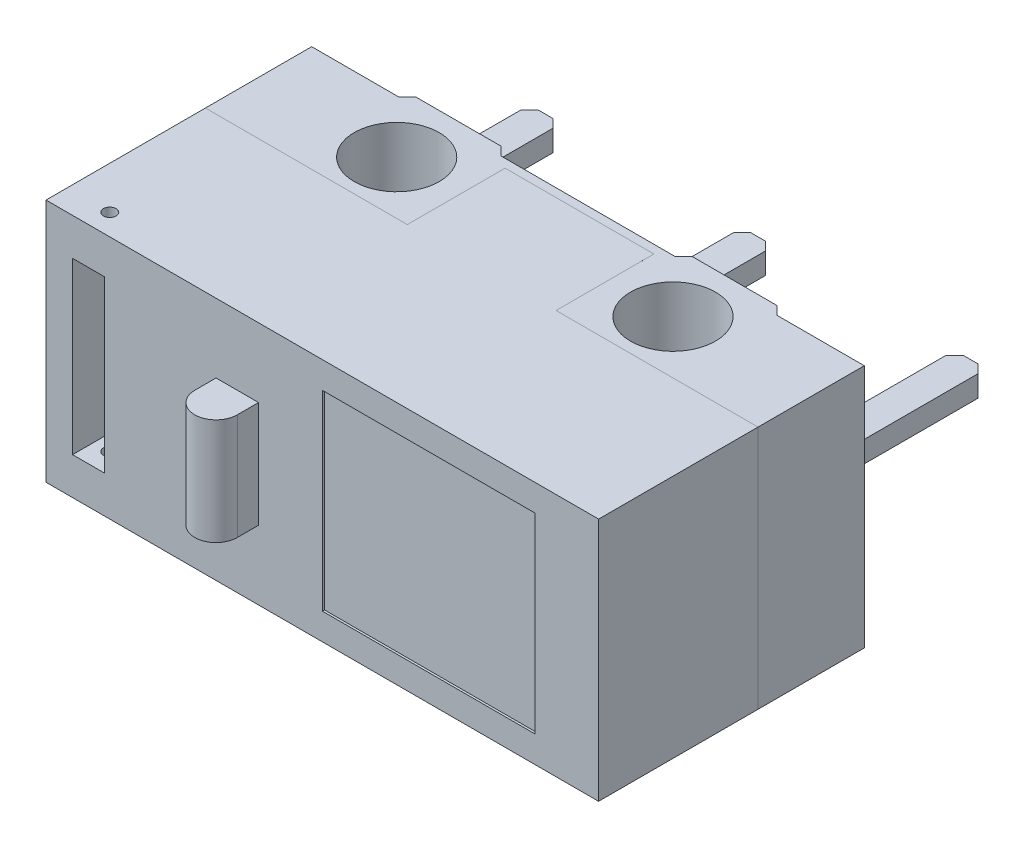
SolidWorks part; units mm, degrees
ref_plane "Front Plane" through (0, 0, 0) normal (0, 0, 1) x (1, 0, 0)
ref_plane "Top Plane" through (0, 0, 0) normal (0, 1, 0) x (1, 0, 0)
ref_plane "Right Plane" through (0, 0, 0) normal (1, 0, 0) x (0, 0, -1)
sketch "Sketch1" plane through (0, 0, 0) normal (0, 0, 1) x (1, 0, 0)
  line L1 (-6.5, 2.875) -> (6.5, 2.875)
  line L2 (-6.5, 2.875) -> (-6.5, -2.875)
  line L3 (-6.5, -2.875) -> (6.5, -2.875)
  line L4 (6.5, 2.875) -> (6.5, -2.875)
  line L5 (-6.5, 2.875) -> (6.5, -2.875) construction
  line L6 (-6.5, -2.875) -> (6.5, 2.875) construction
  point P0 (0, 0)
  dimension "D1" = 13
  dimension "D2" = 5.75
extrude "Boss-Extrude1" add sketch "Sketch1" along normal blind 2.5
sketch "Sketch2" plane through (0, 0, 0) normal (0, 0, -1) x (-1, 0, 0)
  line L1 (-0.375, 0.25) -> (0.375, 0.25)
  line L2 (-0.375, 0.25) -> (-0.375, -0.25)
  line L3 (-0.375, -0.25) -> (0.375, -0.25)
  line L4 (0.375, 0.25) -> (0.375, -0.25)
  line L5 (-0.375, 0.25) -> (0.375, -0.25) construction
  line L6 (-0.375, -0.25) -> (0.375, 0.25) construction
  line L7 (-5.375, 0.25) -> (-4.625, 0.25)
  line L8 (-5.375, 0.25) -> (-5.375, -0.25)
  line L9 (-5.375, -0.25) -> (-4.625, -0.25)
  line L10 (-4.625, 0.25) -> (-4.625, -0.25)
  line L11 (-5.375, 0.25) -> (-4.625, -0.25) construction
  line L12 (-5.375, -0.25) -> (-4.625, 0.25) construction
  line L13 (4.625, 0.25) -> (5.375, 0.25)
  line L14 (4.625, 0.25) -> (4.625, -0.25)
  line L15 (4.625, -0.25) -> (5.375, -0.25)
  line L16 (5.375, 0.25) -> (5.375, -0.25)
  line L17 (4.625, 0.25) -> (5.375, -0.25) construction
  line L18 (4.625, -0.25) -> (5.375, 0.25) construction
  point P0 (0, 0)
  point P6 (-5, 0)
  point P11 (5, 0)
  dimension "D1" = 0.5
  dimension "D2" = 0.5
  dimension "D3" = 0.5
  dimension "D4" = 0.75
  dimension "D5" = 0.75
  dimension "D6" = 0.75
  dimension "D7" = 5
  dimension "D8" = 5
  dimension "D9" = 0
  dimension "D10" = 0
extrude "Boss-Extrude2" add sketch "Sketch2" along normal blind 4
chamfer "Chamfer1" distance 0.2 angle 45 6 edges at (-5.375, 0, -4) (-4.625, 0, -4) (-0.375, 0, -4) (0.375, 0, -4) (4.625, 0, -4) (5.375, 0, -4)
sketch "Sketch4" plane through (0, 2.875, 0) normal (0, 1, 0) x (1, 0, 0)
  line L0 (6.5, 0) -> (-6.5, 0) construction
  circle A0 centre (-3.25, -1.25) radius 1
  circle A1 centre (3.25, -1.25) radius 1
  dimension "D5" = 2
  dimension "D6" = 2
  dimension "D1" = 6.5
  dimension "D2" = 3.25
  dimension "D3" = 1.25
  dimension "D4" = 1.25
extrude "Cut-Extrude1" cut sketch "Sketch4" against normal blind 6
sketch "Sketch5" plane through (0, 2.875, 0) normal (0, 1, 0) x (1, 0, 0)
  line L0 (6.5, 0) -> (-6.5, 0) construction
  line L1 (-4.25, 0) -> (-2.25, 0)
  line L2 (-4.25, 0) -> (-4.25, 0.2)
  line L3 (-4.25, 0.2) -> (-2.25, 0.2)
  line L4 (-2.25, 0) -> (-2.25, 0.2)
  line L5 (4.25, 0) -> (2.25, 0)
  line L6 (4.25, 0) -> (4.25, 0.2)
  line L7 (4.25, 0.2) -> (2.25, 0.2)
  line L8 (2.25, 0) -> (2.25, 0.2)
  circle A0 centre (-3.25, -1.25) radius 1 construction
  circle A1 centre (3.25, -1.25) radius 1 construction
  dimension "D1" = 2
  dimension "D2" = 2
  dimension "D3" = 0
  dimension "D4" = 0
  dimension "D5" = 1
  dimension "D6" = 1
  dimension "D7" = 0.2
  dimension "D8" = 0.2
extrude "Boss-Extrude3" add sketch "Sketch5" against normal blind 5.75
chamfer "Chamfer2" distance 0.2 angle 45 4 edges at (4.25, 0, 0) (2.25, 0, 0) (-2.25, 0, 0) (-4.25, 0, 0)
sketch "Sketch10" plane through (0, 0, 2.5) normal (0, 0, 1) x (1, 0, 0)
  line L0 (-6.5, 2.875) -> (-6.5, -2.875) construction
  line L1 (-6.5001, 2.8751) -> (6.5001, 2.8751)
  line L2 (-6.5001, 2.8751) -> (-6.5001, -2.8751)
  line L3 (-6.5001, -2.8751) -> (6.5001, -2.8751)
  line L4 (6.5001, 2.8751) -> (6.5001, -2.8751)
  line L5 (6.5, 2.875) -> (-6.5, 2.875) construction
  line L6 (6.5, -2.875) -> (6.5, 2.875) construction
  line L7 (-6.5, -2.875) -> (6.5, -2.875) construction
  dimension "D1" = 0.0001
  dimension "D2" = 0.0001
  dimension "D3" = 0.0001
  dimension "D4" = 0.0001
extrude "Boss-Extrude8" add sketch "Sketch10" along normal blind 3.75
sketch "Sketch11" plane through (0, -2.8751, 0) normal (0, -1, 0) x (1, 0, 0)
  line L0 (-6.5, 2.5) -> (6.5, 2.5) construction
  line L1 (-1.75, 2.5) -> (1.75, 2.5)
  line L2 (-1.75, 2.5) -> (-1.75, 0.2)
  line L3 (-1.75, 0.2) -> (1.75, 0.2)
  line L4 (1.75, 2.5) -> (1.75, 0.2)
  line L5 (-2.05, 0) -> (2.05, 0) construction
  point P8 (0, 0)
  dimension "D1" = 3.5
  dimension "D2" = 0
  dimension "D3" = 0.2
  dimension "D4" = 1.75
extrude "Boss-Extrude9" add sketch "Sketch11" against normal blind 0.5
sketch "Sketch12" plane through (0, 2.8751, 0) normal (0, 1, 0) x (1, 0, 0)
  line L0 (6.5, -2.5) -> (-6.5, -2.5) construction
  line L1 (1.75, -2.5) -> (-1.75, -2.5)
  line L2 (1.75, -2.5) -> (1.75, -0.2)
  line L3 (1.75, -0.2) -> (-1.75, -0.2)
  line L4 (-1.75, -2.5) -> (-1.75, -0.2)
  line L5 (2.05, 0) -> (-2.05, 0) construction
  point P8 (0, 0)
  dimension "D1" = 0
  dimension "D2" = 0.2
  dimension "D3" = 1.75
  dimension "D4" = 3.5
extrude "Boss-Extrude10" add sketch "Sketch12" against normal blind 0.5
sketch "Sketch13" plane through (0, 0, 6.25) normal (0, 0, 1) x (1, 0, 0)
  line L0 (6.5001, -2.8751) -> (6.5001, 2.8751) construction
  line L1 (-2.4999, 1.25) -> (-1.4999, 1.25)
  line L2 (-2.4999, 1.25) -> (-2.4999, -1.25)
  line L3 (-2.4999, -1.25) -> (-1.4999, -1.25)
  line L4 (-1.4999, 1.25) -> (-1.4999, -1.25)
  dimension "D1" = 2.5
  dimension "D2" = 1.25
  dimension "D3" = 1
  dimension "D4" = 9
extrude "Boss-Extrude11" add sketch "Sketch13" along normal blind 1
fillet "Fillet2" 2 edges at (-2.4999, 0, 7.25) (-1.4999, 0, 7.25) type full round first side face at (-2.4999, 0, 6.75) second side face at (-1.4999, 0, 6.75) middle face at (-1.9999, 0, 7.25)
sketch "Sketch14" plane through (0, 0, 6.25) normal (0, 0, 1) x (1, 0, 0)
  line L0 (6.5001, -2.8751) -> (6.5001, 2.8751) construction
  line L1 (0.0001, 2.25) -> (5.0001, 2.25)
  line L2 (0.0001, 2.25) -> (0.0001, -2.25)
  line L3 (0.0001, -2.25) -> (5.0001, -2.25)
  line L4 (5.0001, 2.25) -> (5.0001, -2.25)
  dimension "D1" = 5
  dimension "D2" = 4.5
  dimension "D3" = 2.25
  dimension "D4" = 1.5
extrude "Cut-Extrude2" cut sketch "Sketch14" against normal blind 0.05
sketch "Sketch15" plane through (0, 2.8751, 0) normal (0, 1, 0) x (1, 0, 0)
  line L0 (-6.5001, -6.25) -> (-6.5, -2.5) construction
  line L1 (6.5001, -6.25) -> (-6.5001, -6.25) construction
  circle A0 centre (-5.5001, -5.75) radius 0.15
  dimension "D1" = 0.3
  dimension "D2" = 1
  dimension "D3" = 0.5
extrude "Cut-Extrude3" cut sketch "Sketch15" against normal blind 10
sketch "Sketch16" plane through (0, 0, 6.25) normal (0, 0, 1) x (1, 0, 0)
  line L0 (-6.5001, 2.8751) -> (-6.5001, -2.8751) construction
  line L1 (-5.8751, 2) -> (-5.1251, 2)
  line L2 (-5.8751, 2) -> (-5.8751, -2)
  line L3 (-5.8751, -2) -> (-5.1251, -2)
  line L4 (-5.1251, 2) -> (-5.1251, -2)
  line L5 (-5.8751, 2) -> (-5.1251, -2) construction
  line L6 (-5.8751, -2) -> (-5.1251, 2) construction
  point P0 (-5.5001, 0)
  dimension "D1" = 0.75
  dimension "D2" = 1
  dimension "D3" = 4
extrude "Cut-Extrude4" cut sketch "Sketch16" against normal blind 1.2
